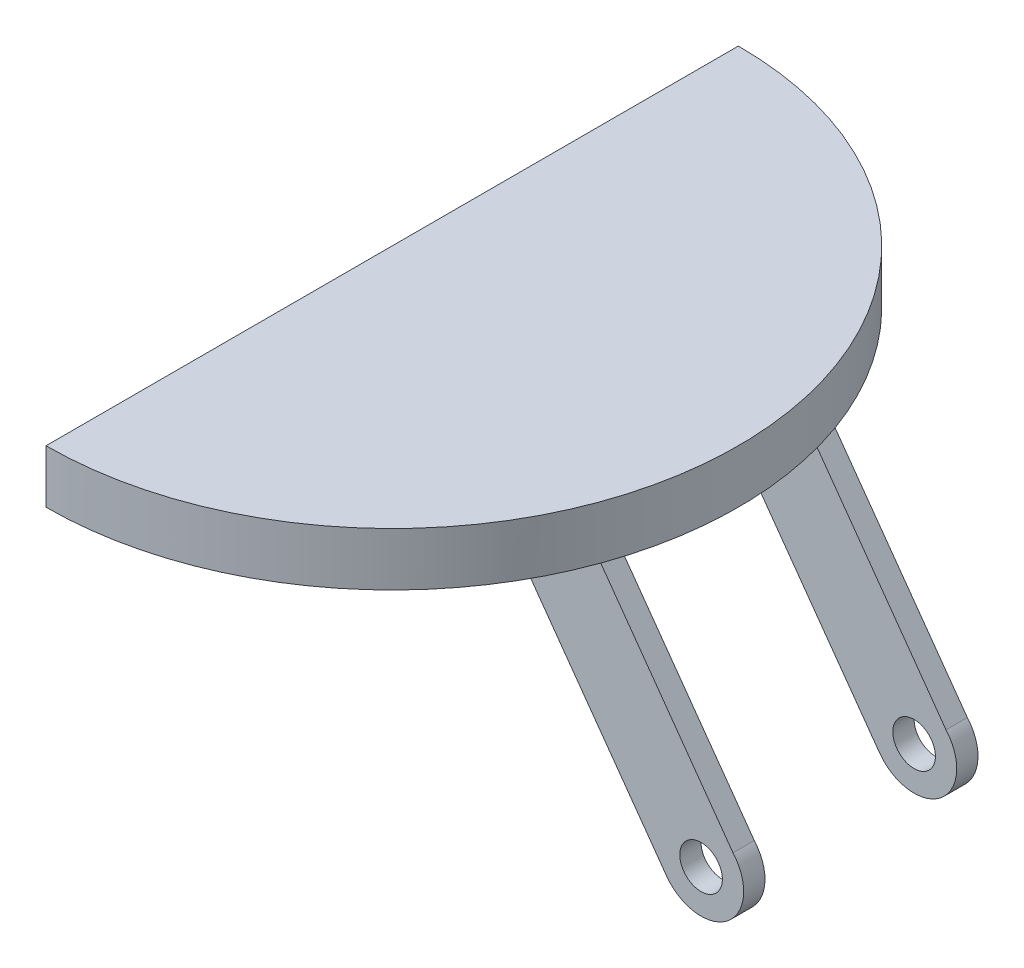
SolidWorks part; units mm, degrees
ref_plane "Ebene vorne" through (0, 0, 0) normal (0, 0, 1) x (1, 0, 0)
ref_plane "Ebene oben" through (0, 0, 0) normal (0, 1, 0) x (1, 0, 0)
ref_plane "Ebene rechts" through (0, 0, 0) normal (1, 0, 0) x (0, 0, -1)
sketch "Skizze1" plane through (0, 0, 0) normal (0, 1, 0) x (1, 0, 0)
  line L0 (0, 0) -> (0, -65)
  arc A0 (0, -65) -> (0, 0) centre (0, -32.5) ccw
  dimension "D1" = 65
extrude "Aufsatz-Linear austragen1" add sketch "Skizze1" along normal blind 5
sketch "Skizze10" plane through (0, 0, 0) normal (0, -1, 0) x (1, 0, 0)
  line L0 (30.5819, 43.5) -> (30.5819, 21.5)
  line L1 (0, 0) -> (0, 65) construction
  arc A0 (0, 0) -> (0, 65) centre (0, 32.5) ccw construction
  dimension "D1" = 22
ref_plane "Ebene1" through (30.5819, 0, 43.5) normal (0, 0, 1) x (1, 0, 0)
sketch "Skizze12" plane through (30.5819, 0, 43.5) normal (0, 0, 1) x (1, 0, 0)
  line L0 (0, 0) -> (12.4162, -17.352)
  line L2 (6.1651, -22.3277) -> (-9.8113, 0)
  line L3 (-9.8113, 0) -> (0, 0)
  line L4 (-30.5819, 8.8878) -> (-30.5819, -28.7638) construction
  line L5 (9.4181, -15.4311) -> (9.4181, -25.351) construction
  line L6 (4.832, -20) -> (14.1192, -20) construction
  arc A0 (6.1651, -22.3277) -> (12.4162, -17.352) centre (9.4181, -20) ccw
  point P13 (4.832, -20)
  point P14 (14.1192, -20)
  point P15 (0, 0)
  point P16 (0, 0)
  point P17 (0, 0)
  dimension "D1" = 40
  dimension "D2" = 4
  dimension "D3" = 20
extrude "Aufsatz-Linear austragen2" add sketch "Skizze12" against normal up to vertex (22 mm away) contours L0 A0 L2 L3 up to point (30.5819, 0, 21.5)
sketch "Skizze13" plane through (30.5819, 0, 43.5) normal (0, 0, 1) x (1, 0, 0)
  circle A4 centre (9.4181, -20) radius 2
  arc A5 (6.1651, -22.3277) -> (12.4162, -17.352) centre (9.4181, -20) ccw construction
extrude "Schnitt-Linear austragen1" cut sketch "Skizze13" against normal up to surface (22 mm away) up to face at (33.429, -10.7424, 21.5)
ref_plane "Ebene2" through (20.7705, 0, 21.5) normal (1, 0, 0) x (0, 0, -1)
sketch "Skizze14" plane through (20.7705, 0, 21.5) normal (1, 0, 0) x (0, 0, -1)
  line L0 (-22, 0) -> (0, 0) construction
  line L1 (-2, 0) -> (-20, 0)
  line L2 (-2, 0) -> (-2, -24)
  line L3 (-2, -24) -> (-20, -24)
  line L4 (-20, 0) -> (-20, -24)
  line L5 (-22, -24) -> (0, -24) construction
  line L6 (-11, 32.6837) -> (-11, -32.3163) construction
  line L7 (0, -22.3277) -> (0, 0) construction
  line L8 (-22, -22.3277) -> (-22, 0) construction
  line L9 (0, 0) -> (0, -17.352) construction
  line L12 (-43.5, 5) -> (-43.5, 0) construction
  line L13 (21.5, 5) -> (21.5, 0) construction
  point P10 (0, 0)
  dimension "D1" = 2
extrude "Schnitt-Linear austragen4" cut sketch "Skizze14" along normal through all
sketch "Skizze9" plane through (0, 0, 29.4822) normal (0, 0, -1) x (-1, 0, 0)
